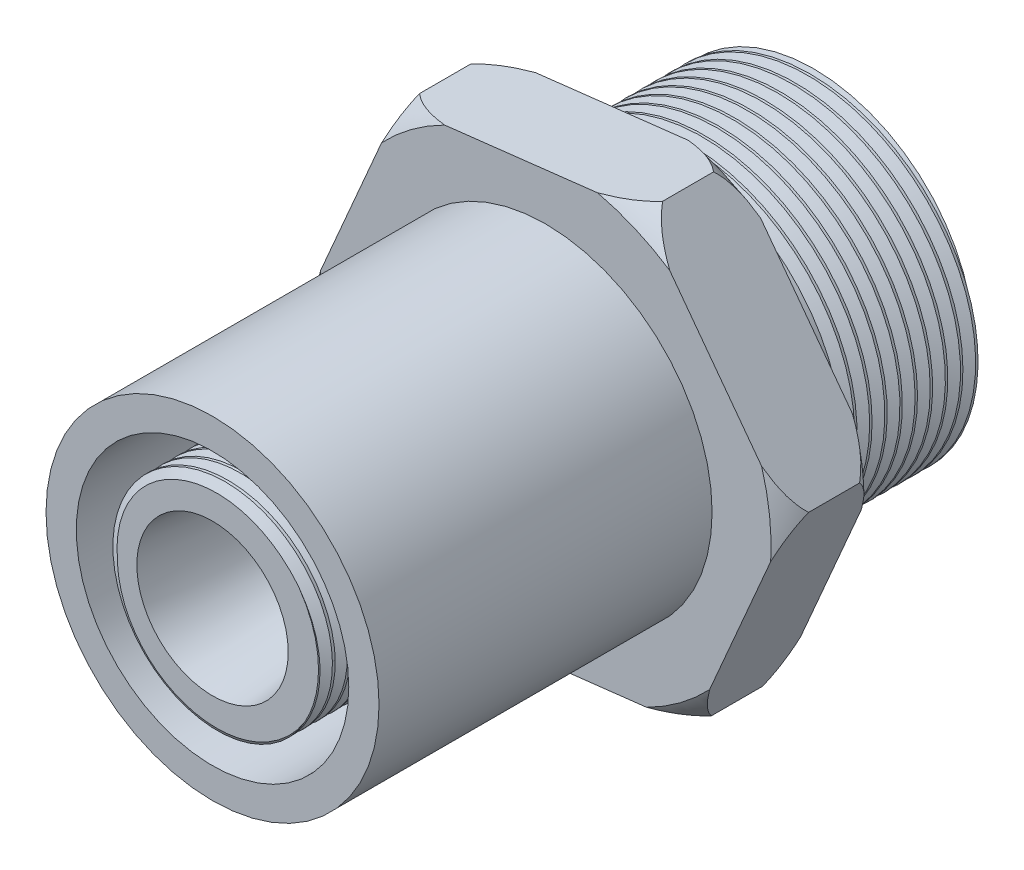
SolidWorks part; units mm, degrees
ref_plane "Front Plane" through (0, 0, 0) normal (0, 0, 1) x (1, 0, 0)
ref_plane "Top Plane" through (0, 0, 0) normal (0, 1, 0) x (1, 0, 0)
ref_plane "Right Plane" through (0, 0, 0) normal (1, 0, 0) x (0, 0, -1)
sketch "Sketch1" plane through (0, 0, 0) normal (0, 0, 1) x (1, 0, 0)
  circle A0 centre (0, 0) radius 2.75
  dimension "D1" = 5.5
extrude "Boss-Extrude1" add sketch "Sketch1" along normal blind 10
sketch "Sketch2" plane through (0, 0, 0) normal (0, 0, -1) x (-1, 0, 0)
  circle A0 centre (0, 0) radius 2.75 construction
  circle A1 centre (0, 0) radius 2.75
curve "Helix/Spiral1" pitch 0.25 height 2.5 turns 10
ref_plane "Plane1" through (2.75, 0, 0) normal (0, 0.9999, 0.0145) x (1, 0, 0)
sketch "Sketch3" plane through (2.75, 0, 0) normal (0, 0.9999, 0.0145) x (1, 0, 0)
  line L1 (-0.1821, -0.0034) -> (0.0084, -0.1134)
  line L2 (0.0084, -0.1134) -> (0.0084, 0.1066)
  line L3 (0.0084, 0.1066) -> (-0.1821, -0.0034)
  circle A0 centre (-0.0551, -0.0034) radius 0.0635 construction
  dimension ".22" = 0.22
sweep "Cut-Sweep1" cut profiles "Sketch3" path "Helix/Spiral1"
ref_plane "Plane2" through (0, 0, 0) normal (0, 0, -1) x (-1, 0, 0)
ref_plane "Plane3" through (0, 0, 2.5) normal (0, 0, -1) x (-1, 0, 0)
sketch "Sketch4" plane through (0, 0, 2.5) normal (0, 0, -1) x (-1, 0, 0)
  circle A0 centre (0, 0) radius 3.4881
  circle A2 centre (0, 0) radius 2.4
  dimension "D1" = 4.8
extrude "Cut-Extrude2" cut sketch "Sketch4" against normal blind 0.5
sketch "Sketch5" plane through (0, 0, 3) normal (0, 0, -1) x (-1, 0, 0)
  line L1 (-1.603, 3.71) -> (-4.0144, 0.4668)
  line L2 (-4.0144, 0.4668) -> (-2.4114, -3.2432)
  line L3 (-2.4114, -3.2432) -> (1.603, -3.71)
  line L4 (1.603, -3.71) -> (4.0144, -0.4668)
  line L5 (4.0144, -0.4668) -> (2.4114, 3.2432)
  line L6 (2.4114, 3.2432) -> (-1.603, 3.71)
  circle A0 centre (0, 0) radius 3.5 construction
  dimension "D1" = 7
extrude "Boss-Extrude3" add sketch "Sketch5" against normal blind 1.5
sketch "Sketch7" plane through (0, 0, 0) normal (0, 0, -1) x (-1, 0, 0)
  circle A0 centre (0, 0) radius 0.5
  dimension "D1" = 1
extrude "Cut-Extrude3" cut sketch "Sketch7" against normal blind 11.5
sketch "Sketch8" plane through (0, 0, 10) normal (0, 0, 1) x (1, 0, 0)
  circle A2 centre (0, 0) radius 1.25
  dimension "D1" = 2.5
extrude "Cut-Extrude4" cut sketch "Sketch8" against normal up to surface (5.5 mm away) draft 6
sketch "Sketch9" plane through (0, 0, 0) normal (0, 0, -1) x (-1, 0, 0)
  circle A0 centre (0, 0) radius 1.25
  circle A1 centre (0, 0) radius 2.75 construction
  dimension "D1" = 2.5
extrude "Cut-Extrude5" cut sketch "Sketch9" against normal blind 2
sketch "Sketch10" plane through (0, 0, 3) normal (0, 0, -1) x (-1, 0, 0)
  circle A0 centre (0, 0) radius 4.0415
ref_plane "Plane4" through (0, 0, 0) normal (0.918, -0.3966, 0) x (0, 0, -1)
sketch "Sketch11" plane through (0, 0, 0) normal (0.918, -0.3966, 0) x (0, 0, -1)
  line L0 (-3.75, -4.0415) -> (-3.75, -5.5675) construction
  line L1 (-4.5, -4.0415) -> (-3, -4.0415) construction
  line L2 (-2.835, -3.1286) -> (-2.835, -4.1851)
  line L3 (-2.835, -4.1851) -> (-3.4985, -4.1851)
  line L4 (-3.4985, -4.119) -> (-3.4985, -4.1851)
  line L6 (-4.0015, -4.119) -> (-4.0015, -4.1851)
  line L7 (-4.665, -4.1851) -> (-4.0015, -4.1851)
  line L8 (-4.665, -3.1286) -> (-4.665, -4.1851)
  spline S0 degree 3 poles (-2.835, -3.1286) (-2.8637, -3.639) (-3.0848, -3.9691) (-3.4985, -4.119) knots 0 0 0 0 0.839892 0.839892 0.839892 0.839892
  spline S1 degree 3 poles (-4.665, -3.1286) (-4.6363, -3.639) (-4.4152, -3.9691) (-4.0015, -4.119) knots 0 0 0 0 0.839892 0.839892 0.839892 0.839892
sweep "Cut-Sweep2" cut profiles "Sketch11" path "Sketch10"
sketch "Sketch12" plane through (0, 0, 10) normal (0, 0, 1) x (1, 0, 0)
  circle A2 centre (0, 0) radius 1.75
  circle A3 centre (0, 0) radius 2.25
  dimension "D1" = 3.5
  dimension "D2" = 4.5
extrude "Cut-Extrude6" cut sketch "Sketch12" against normal blind 4
sketch "Sketch13" plane through (0, 0, 10) normal (0, 0, 1) x (1, 0, 0)
  circle A0 centre (0, 0) radius 1.75 construction
  circle A1 centre (0, 0) radius 1.75
curve "Helix/Spiral2" pitch 0.25 height 3.5 turns 14
ref_plane "Plane5" through (-1.75, 0, 10) normal (0, 0.9997, -0.0227) x (1, 0, 0)
sketch "Sketch14" plane through (-1.75, 0, 10) normal (0, 0.9997, -0.0227) x (1, 0, 0)
  line L1 (0.1774, 0.0021) -> (-0.0131, 0.1121)
  line L2 (-0.0131, 0.1121) -> (-0.0131, -0.1079)
  line L3 (-0.0131, -0.1079) -> (0.1774, 0.0021)
  circle A0 centre (0.0504, 0.0021) radius 0.0635 construction
  point P1 (0, 0)
  point P7 (0.0329, -0.0028)
  point P8 (0.0504, 0.0021)
  dimension "D1" = 0.22
sweep "Cut-Sweep3" cut profiles "Sketch14" path "Helix/Spiral2"
